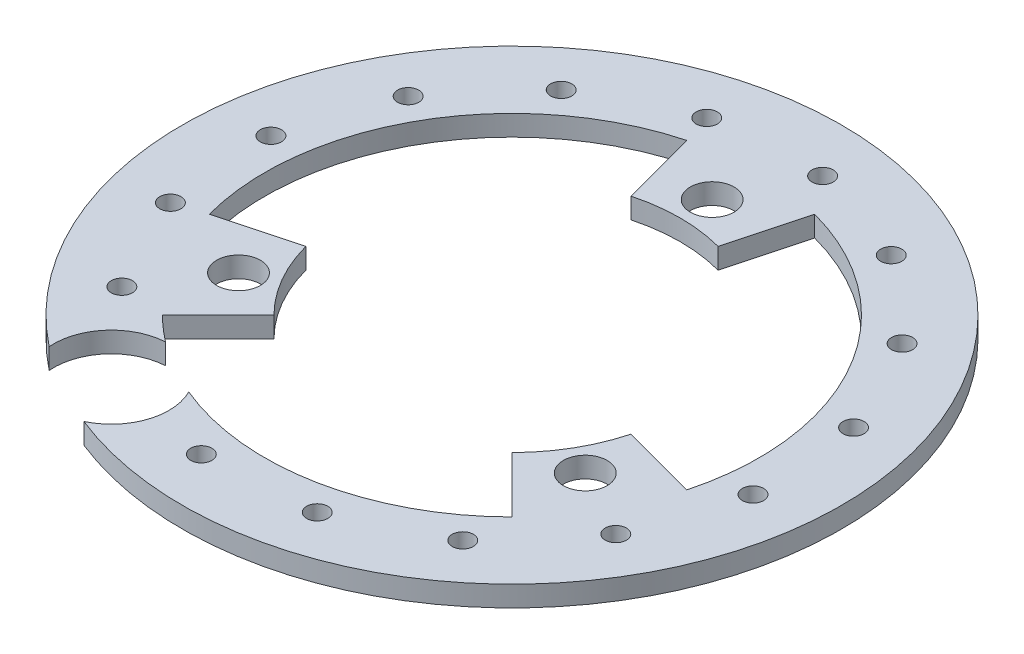
SolidWorks part; units mm, degrees
note: '?' marks a value the reader was unsure of.
ref_plane "Front Plane" through (0, 0, 0) normal (0, 0, 1) x (1, 0, 0)
ref_plane "Top Plane" through (0, 0, 0) normal (0, 1, 0) x (1, 0, 0)
ref_plane "Right Plane" through (0, 0, 0) normal (1, 0, 0) x (0, 0, -1)
sketch "Sketch1" plane through (0, 0, 0) normal (0, 1, 0) x (1, 0, 0)
  circle A0 centre (0, 0) radius 101.6
extrude "Extrude1" add sketch "Sketch1" along normal blind 6.35
sketch "Sketch3" plane through (0, 0, 0) normal (0, 1, 0) x (1, 0, 0)
  circle A0 centre (0, 0) radius 51.8922
  dimension "D1" = 103.7844
extrude "Cut-Extrude2" cut sketch "Sketch3" along normal blind 6.35
sketch "Sketch4" plane through (0, 0, 0) normal (0, 1, 0) x (1, 0, 0)
  line L0 (0, 0) -> (0, 61.722)
  dimension "D1" = 61.722
sketch "Sketch5" plane through (0, 0, 0) normal (0, 1, 0) x (1, 0, 0)
  circle A0 centre (0, 61.722) radius 6.7469
  dimension "D1" = 13.4937
extrude "Cut-Extrude4" cut sketch "Sketch5" along normal blind 6.35
ref_axis "Axis1" through (0, 104.3147, 0) along (0, -1, 0)?
pattern_circular "CirPattern1" count 3 over 360 about axis through (0, 0, 0) along (0, 1, 0) of "Cut-Extrude4"
sketch "Sketch6" plane through (0, 0, 0) normal (0, 1, 0) x (1, 0, 0)
  line L0 (0, 0) -> (53.4528, -30.861)
sketch "Sketch7" plane through (0, 0, 0) normal (0, 0, 1) x (1, 0, 0)
  line L0 (0, 0) -> (0, -17.2214)
sketch "Sketch8" plane through (0, 0, 0) normal (0, 1, 0) x (1, 0, 0)
  line L0 (0, 0) -> (-45.212, -78.3095)
  line L1 (0, 0) -> (53.4528, -30.861) construction
  dimension "D1" = 90
  dimension "D2" = 90.424
sketch "Sketch13" plane through (0, 0, 0) normal (0, 1, 0) x (1, 0, 0)
  circle A0 centre (0, 0) radius 101.6
  circle A1 centre (0, 0) radius 51.8922
  dimension "D1" = 103.7844
sketch "Sketch16" plane through (0, 0, 0) normal (0, 1, 0) x (1, 0, 0)
  circle A0 centre (-45.212, -78.3095) radius 17.78
  dimension "D1" = 35.56
extrude "Cut-Extrude5" cut sketch "Sketch16" along normal blind 6.35
sketch "Sketch17" plane through (0, 0, 0) normal (0, 1, 0) x (1, 0, 0)
  line L0 (0, 0) -> (-53.4528, -30.861)
  line L1 (-19.722, 73.6035) -> (0, 0)
  line L2 (0, 0) -> (0.6211, -0.5077)
  line L3 (-73.6035, -19.722) -> (0, 0)
  line L4 (0, 0) -> (0.2877, 0.3961)
  line L5 (0, 0) -> (0, 61.722) construction
  arc A0 (-19.722, 73.6035) -> (-73.6035, -19.722) centre (0, 0) ccw
  arc A1 (-13.4307, 50.124) -> (-50.124, -13.4307) centre (0, 0) ccw
  dimension "D1" = 76.2
  dimension "D4" = 51.8922
  dimension "D2" = 15
  dimension "D3" = 15
extrude "Cut-Extrude9" cut sketch "Sketch17" along normal blind 6.35 contours A1 L1 A0 L3
pattern_circular "CirPattern2" count 3 over 360 about axis through (0, 0, 0) along (0, 1, 0) of "Cut-Extrude9"
sketch "Sketch18" plane through (0, 0, 0) normal (0, 1, 0) x (1, 0, 0)
  line L0 (0, 0) -> (53.4528, -30.861) construction
  line L1 (0, 0) -> (-45.212, -78.3095) construction
  line L2 (0, 0) -> (51.6137, -53.2627)
  line L3 (0, 0) -> (-18.0674, -71.9337)
  line L4 (-18.0674, -71.9337) -> (-17.4734, -71.6486)
  arc A0 (51.6137, -53.2627) -> (-18.0674, -71.9337) centre (0, 0) cw
  arc A1 (36.1119, -37.2657) -> (-12.641, -50.329) centre (0, 0) cw
  dimension "D1" = 74.168
  dimension "D4" = 51.8922
  dimension "D2" = 20.32
  dimension "D3" = 20.32
extrude "Cut-Extrude11" [suppressed] cut sketch "Sketch18" along normal through all
ref_plane "Plane1" through (0, 6.35, 0) normal (0, 1, 0) x (-1, 0, 0)
sketch "Sketch19" plane through (0, 6.35, 0) normal (0, 1, 0) x (-1, 0, 0)
  line L0 (44.661, 78.3328) -> (0, 0)
  line L1 (12.2112, 21.4178) -> (-43.1227, -75.6347)
  circle A0 centre (-42.4594, -74.4713) radius 4.7565
  dimension "D1" = 85.725
hole_wizard "F (0.257) Diameter Hole1" positions "3DSketch2" profile "Sketch23" hole size "F" standard "Ansi Inch"
sketch3d "3DSketch2"
  point P0 (42.4594, 6.35, -74.4713)
sketch "Sketch23" plane through (42.4594, 6.35, -74.4713) normal (1, 0, 0) x (0, 0, 1)
  line L0 (0, 0) -> (0, 60.3811)
  line L1 (0, 60.3811) -> (3.2639, 58.42)
  line L2 (3.2639, 58.42) -> (3.2639, 0)
  line L5 (3.2639, 0) -> (0, 0)
  line L10 (0, 60.3811) -> (-3.2639, 58.42) construction
  line L11 (0, -6.35) -> (0, 107.95) construction
  dimension "Hole Dia." = 6.5278
  dimension "Hole Depth" = 58.42
  dimension "Drill Angle" = 118
pattern_circular "CirPattern3" count 16 over 360 about axis through (0, 0, 0) along (0, 1, 0) skipping 8 of "F (0.257) Diameter Hole1"
